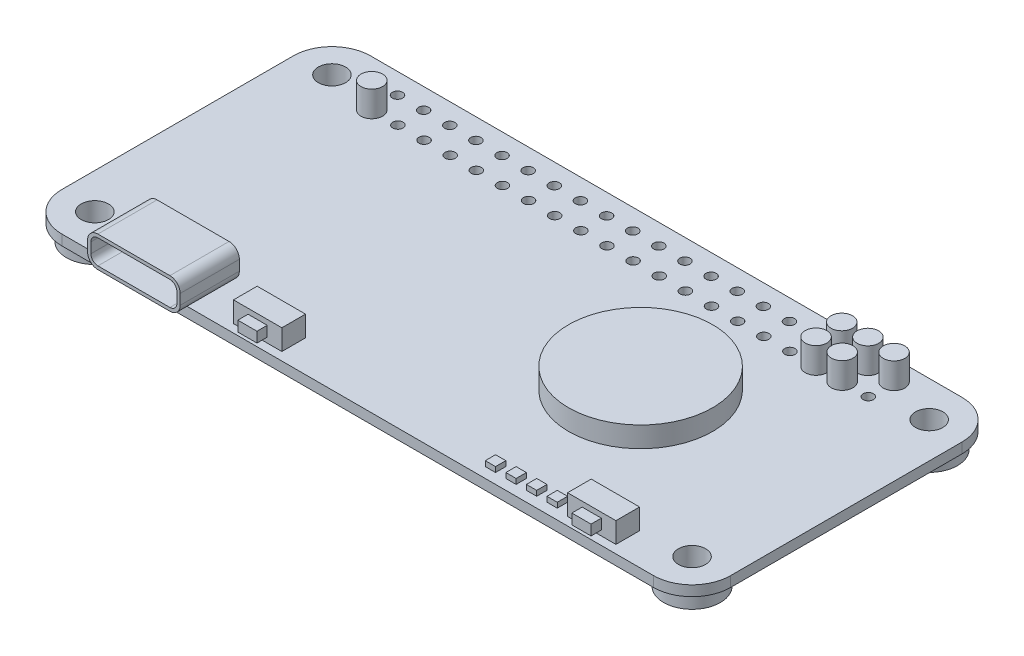
SolidWorks part; units mm, degrees
ref_plane "Front Plane" through (0, 0, 0) normal (0, 0, 1) x (1, 0, 0)
ref_plane "Top Plane" through (0, 0, 0) normal (0, 1, 0) x (1, 0, 0)
ref_plane "Right Plane" through (0, 0, 0) normal (1, 0, 0) x (0, 0, -1)
sketch "Sketch1" plane through (0, 0, 0) normal (0, 1, 0) x (1, 0, 0)
  line L1 (-28.75, 15) -> (28.75, 15)
  line L2 (-32.5, 11.25) -> (-32.5, -11.25)
  line L3 (-28.75, -15) -> (28.75, -15)
  line L4 (32.5, 11.25) -> (32.5, -11.25)
  line L5 (-32.5, 15) -> (32.5, -15) construction
  line L6 (-32.5, -15) -> (32.5, 15) construction
  arc A0 (-32.5, -11.25) -> (-28.75, -15) centre (-28.75, -11.25) ccw
  arc A1 (28.75, -15) -> (32.5, -11.25) centre (28.75, -11.25) ccw
  arc A2 (28.75, 15) -> (32.5, 11.25) centre (28.75, 11.25) cw
  arc A3 (-28.75, 15) -> (-32.5, 11.25) centre (-28.75, 11.25) ccw
  point P0 (0, 0)
  dimension "D3" = 3.75
  dimension "D1" = 65
  dimension "D2" = 30
extrude "Boss-Extrude1" add sketch "Sketch1" along normal blind 1 contours L1 A2 L4 A1 L3 A0 L2 A3
sketch "Sketch2" plane through (0, 1, 0) normal (0, 1, 0) x (1, 0, 0)
  line L0 (0, 15) -> (0, -15) construction
  line L1 (-28.75, 15) -> (28.75, 15) construction
  line L2 (-28.75, -15) -> (28.75, -15) construction
  line L3 (-32.5, 0) -> (32.5, 0) construction
  line L4 (-32.5, 11.25) -> (-32.5, -11.25) construction
  line L5 (32.5, 11.25) -> (32.5, -11.25) construction
  circle A0 centre (-29.025, 11.525) radius 1.325
  circle A2 centre (29.025, 11.525) radius 1.325
  circle A3 centre (29.025, -11.525) radius 1.325
  circle A4 centre (-29.025, -11.525) radius 1.325
  dimension "D1" = 2.65
  dimension "D2" = 2.15
  dimension "D3" = 2.15
extrude "Cut-Extrude1" cut sketch "Sketch2" against normal through all
sketch "Sketch3" plane through (0, 1, 0) normal (0, 1, 0) x (1, 0, 0)
  line L0 (-24.128, 13) -> (-24.128, 10.5) construction
  line L3 (-28.75, 15) -> (28.75, 15) construction
  line L5 (-32.5, 11.25) -> (-32.5, -11.25) construction
  circle A0 centre (-24.128, 13) radius 0.5
  circle A1 centre (-24.128, 10.5) radius 0.5
  dimension "D1" = 1
  dimension "D3" = 1.5
  dimension "D4" = 7.872
  dimension "D2" = 2.5
extrude "Cut-Extrude2" cut sketch "Sketch3" against normal through all
pattern_linear "LPattern1" count 20 spacing 2.54 along (1, 0, 0) of "Cut-Extrude2"
sketch "Sketch15" plane through (0, 0, 15) normal (0, 0, 1) x (1, 0, 0)
  line L0 (-28.75, 1) -> (28.75, 1) construction
  line L2 (-24, 4) -> (-17, 4)
  line L3 (-25, 3) -> (-25, 2)
  line L4 (-24, 1) -> (-17, 1)
  line L5 (-16, 3) -> (-16, 2)
  line L6 (-32.5, 1) -> (-32.5, 0) construction
  line L9 (15.325, 0) -> (15.325, 5.5788) construction
  line L10 (-28.75, 0) -> (28.75, 0) construction
  arc A0 (-17, 4) -> (-16, 3) centre (-17, 3) cw
  arc A1 (-17, 1) -> (-16, 2) centre (-17, 2) ccw
  arc A2 (-25, 2) -> (-24, 1) centre (-24, 2) ccw
  arc A3 (-24, 4) -> (-25, 3) centre (-24, 3) ccw
  point P10 (-16, 4)
  point P13 (-16, 1)
  point P18 (-25, 4)
  dimension "D4" = 1
  dimension "D1" = 9
  dimension "D2" = 3
  dimension "D3" = 7.5
extrude "Boss-Extrude6" add sketch "Sketch15" along normal blind 1.25 and the other way blind 4.5
sketch "Sketch16" plane through (0, 0, 16.25) normal (0, 0, 1) x (1, 0, 0)
  line L4 (-17, 3.68) -> (-24, 3.68)
  line L5 (-17, 3.68) -> (-24, 3.68)
  line L6 (-24.68, 3) -> (-24.68, 2)
  line L7 (-24.68, 3) -> (-24.68, 2)
  line L8 (-24, 1.32) -> (-17, 1.32)
  line L9 (-24, 1.32) -> (-17, 1.32)
  line L10 (-16.32, 2) -> (-16.32, 3)
  line L11 (-16.32, 2) -> (-16.32, 3)
  arc A4 (-16.32, 3) -> (-17, 3.68) centre (-17, 3) ccw
  arc A5 (-16.32, 3) -> (-17, 3.68) centre (-17, 3) ccw
  arc A6 (-24, 3.68) -> (-24.68, 3) centre (-24, 3) ccw
  arc A7 (-24, 3.68) -> (-24.68, 3) centre (-24, 3) ccw
  arc A8 (-24.68, 2) -> (-24, 1.32) centre (-24, 2) ccw
  arc A9 (-24.68, 2) -> (-24, 1.32) centre (-24, 2) ccw
  arc A10 (-17, 1.32) -> (-16.32, 2) centre (-17, 2) ccw
  arc A11 (-17, 1.32) -> (-16.32, 2) centre (-17, 2) ccw
  dimension "D2" = 0.32
extrude "Cut-Extrude9" cut sketch "Sketch16" against normal blind 5.25
sketch "草图1" plane through (0, 1, 0) normal (0, 1, 0) x (1, 0, 0)
  line L1 (-12.87, -11.9) -> (-8.17, -11.9)
  line L2 (-12.87, -11.9) -> (-12.87, -14.2)
  line L3 (-12.87, -14.2) -> (-8.17, -14.2)
  line L4 (-8.17, -11.9) -> (-8.17, -14.2)
  line L5 (-28.75, -15) -> (-24, -15) construction
  line L6 (-16, -10.5) -> (-16, -16.25) construction
  line L7 (32.5, 11.25) -> (32.5, -11.25) construction
  line L8 (24.3, -11.9) -> (19.6, -11.9)
  line L9 (24.3, -11.9) -> (24.3, -14.2)
  line L10 (24.3, -14.2) -> (19.6, -14.2)
  line L11 (19.6, -11.9) -> (19.6, -14.2)
  dimension "D1" = 4.7
  dimension "D2" = 2.3
  dimension "D3" = 3.13
  dimension "D4" = 0.8
  dimension "D5" = 8.2
extrude "凸台-拉伸1" add sketch "草图1" along normal blind 2
sketch "草图2" plane through (0, 0, 14.2) normal (0, 0, 1) x (1, 0, 0)
  line L0 (-12.87, 3) -> (-8.17, 3) construction
  line L5 (-11.45, 2.5) -> (-9.59, 2.5)
  line L6 (-11.45, 2.5) -> (-11.45, 1.5)
  line L7 (-11.45, 1.5) -> (-9.59, 1.5)
  line L8 (-9.59, 2.5) -> (-9.59, 1.5)
  line L9 (-11.45, 2.5) -> (-9.59, 1.5) construction
  line L10 (-11.45, 1.5) -> (-9.59, 2.5) construction
  line L11 (-8.17, 3) -> (-8.17, 1) construction
  line L12 (19.6, 3) -> (24.3, 3) construction
  line L13 (21.02, 2.5) -> (22.88, 2.5)
  line L14 (21.02, 2.5) -> (21.02, 1.5)
  line L15 (21.02, 1.5) -> (22.88, 1.5)
  line L16 (22.88, 2.5) -> (22.88, 1.5)
  line L17 (21.02, 2.5) -> (22.88, 1.5) construction
  line L18 (21.02, 1.5) -> (22.88, 2.5) construction
  line L19 (24.3, 3) -> (24.3, 1) construction
  point P0 (-10.52, 2)
  point P5 (21.95, 2)
  point P8 (-10.52, 3)
  point P12 (-8.17, 2)
  point P19 (21.95, 3)
  point P23 (24.3, 2)
  dimension "D1" = 1.86
  dimension "D2" = 1
extrude "凸台-拉伸2" add sketch "草图2" along normal blind 1
sketch "草图9" plane through (0, 0, 0) normal (0, -1, 0) x (1, 0, 0)
  circle A0 centre (29.025, 11.525) radius 2.75
  circle A1 centre (29.025, -11.525) radius 2.75
  circle A2 centre (-29.025, 11.525) radius 2.75
  circle A3 centre (-29.025, -11.525) radius 2.75
  circle A4 centre (29.025, 11.525) radius 1.325 construction
  circle A5 centre (29.025, -11.525) radius 1.325 construction
  circle A6 centre (-29.025, 11.525) radius 1.325 construction
  circle A7 centre (-29.025, -11.525) radius 1.325 construction
  circle A8 centre (29.025, 11.525) radius 1.325
  circle A9 centre (29.025, -11.525) radius 1.325
  circle A10 centre (-29.025, 11.525) radius 1.325
  circle A11 centre (-29.025, -11.525) radius 1.325
  dimension "D1" = 5.5
extrude "凸台-拉伸8" add sketch "草图9" along normal blind 1.5
sketch "草图10" plane through (0, 1, 0) normal (0, 1, 0) x (1, 0, 0)
  circle A0 centre (24.132, 13) radius 1.05
  circle A1 centre (21.592, 13) radius 1.05
  circle A2 centre (19.052, 13) radius 1.05
  circle A3 centre (21.592, 10.5) radius 1.05
  circle A4 centre (19.052, 10.5) radius 1.05
  circle A5 centre (-24.128, 10.5) radius 1.05
  dimension "D1" = 2.1
extrude "凸台-拉伸9" add sketch "草图10" along normal blind 2.5
sketch "草图11" plane through (0, 1, 0) normal (0, -1, 0) x (1, 0, 0)
  circle A0 centre (24.132, -13) radius 0.5
  circle A1 centre (21.592, -13) radius 0.5
  circle A2 centre (21.592, -10.5) radius 0.5
  circle A3 centre (19.052, -10.5) radius 0.5
  circle A5 centre (19.052, -13) radius 0.5
  circle A7 centre (-24.128, -10.5) radius 0.5
extrude "凸台-拉伸10" add sketch "草图11" along normal blind 3
sketch "草图12" plane through (0, 1, 0) normal (0, 1, 0) x (1, 0, 0)
  line L1 (32.5, 11.25) -> (32.5, -11.25) construction
  line L2 (-28.75, 15) -> (28.75, 15) construction
  circle A0 centre (12.5, 0) radius 7
  dimension "D1" = 14
  dimension "D2" = 20
  dimension "D3" = 15
extrude "凸台-拉伸11" add sketch "草图12" along normal blind 2
sketch "草图13" plane through (0, 1, 0) normal (0, 1, 0) x (1, 0, 0)
  line L0 (19.6, -11.9) -> (19.6, -14.2) construction
  line L1 (17.4, -13) -> (18.4, -13)
  line L2 (17.4, -13) -> (17.4, -14)
  line L3 (17.4, -14) -> (18.4, -14)
  line L4 (18.4, -13) -> (18.4, -14)
  line L5 (17.4, -13) -> (18.4, -14) construction
  line L6 (17.4, -14) -> (18.4, -13) construction
  line L7 (15.4, -13) -> (16.4, -13)
  line L8 (15.4, -13) -> (15.4, -14)
  line L9 (15.4, -14) -> (16.4, -14)
  line L10 (16.4, -13) -> (16.4, -14)
  line L11 (15.4, -13) -> (16.4, -14) construction
  line L12 (15.4, -14) -> (16.4, -13) construction
  line L13 (13.4, -13) -> (14.4, -13)
  line L14 (13.4, -13) -> (13.4, -14)
  line L15 (13.4, -14) -> (14.4, -14)
  line L16 (14.4, -13) -> (14.4, -14)
  line L17 (13.4, -13) -> (14.4, -14) construction
  line L18 (13.4, -14) -> (14.4, -13) construction
  line L19 (11.4, -13) -> (12.4, -13)
  line L20 (11.4, -13) -> (11.4, -14)
  line L21 (11.4, -14) -> (12.4, -14)
  line L22 (12.4, -13) -> (12.4, -14)
  line L23 (11.4, -13) -> (12.4, -14) construction
  line L24 (11.4, -14) -> (12.4, -13) construction
  line L25 (-17, -15) -> (28.75, -15) construction
  point P0 (17.9, -13.5)
  point P5 (15.9, -13.5)
  point P10 (13.9, -13.5)
  point P15 (11.9, -13.5)
  point P20 (0, 0)
  point P21 (0, 0)
  point P22 (16.9627, -13.3321)
  point P23 (13.5048, -13.4256)
  point P24 (11.0438, -13.4256)
  point P27 (0, 0)
  point P28 (0, 0)
  dimension "D1" = 1
  dimension "D2" = 1
  dimension "D3" = 1
  dimension "D4" = 1
  dimension "D5" = 1
  dimension "D6" = 1.2
  dimension "D7" = 1
extrude "凸台-拉伸12" add sketch "草图13" along normal blind 0.5
